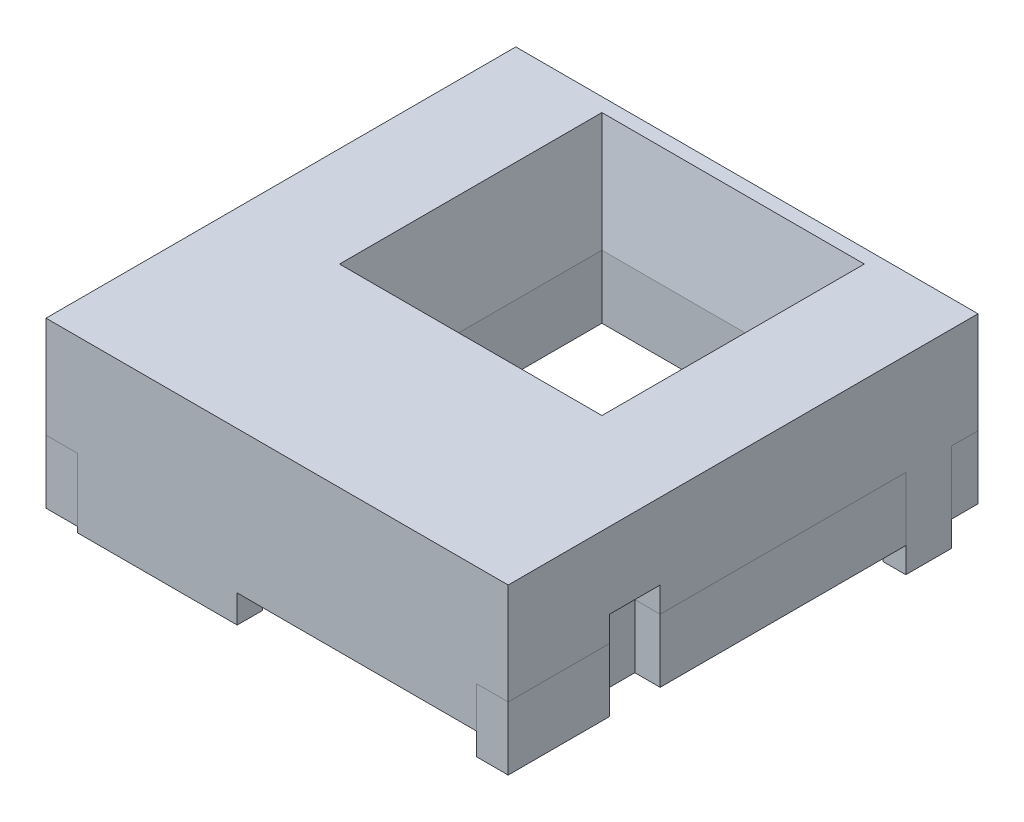
SolidWorks part; units mm, degrees
ref_plane "Front Plane" through (0, 0, 0) normal (0, 0, 1) x (1, 0, 0)
ref_plane "Top Plane" through (0, 0, 0) normal (0, 1, 0) x (1, 0, 0)
ref_plane "Right Plane" through (0, 0, 0) normal (1, 0, 0) x (0, 0, -1)
sketch "Sketch1" plane through (0, 0, 0) normal (0, 1, 0) x (1, 0, 0)
  line L1 (0, 0) -> (36.5, 0)
  line L2 (0, 0) -> (0, -37.1)
  line L3 (0, -37.1) -> (36.5, -37.1)
  line L4 (36.5, 0) -> (36.5, -37.1)
  dimension "D1" = 37.1
  dimension "D2" = 36.5
extrude "Body" add sketch "Sketch1" along normal blind 8
sketch "Sketch2" plane through (0, 0, 0) normal (0, -1, 0) x (-1, 0, 0)
  line L0 (-36.5, 0) -> (0, 0) construction
  line L1 (0, -6.1) -> (-2, -6.1)
  line L2 (0, -6.1) -> (0, -2.1)
  line L3 (0, -2.1) -> (-2, -2.1)
  line L4 (-2, -6.1) -> (-2, -2.1)
  line L5 (-34.5, -29.1) -> (-36.5, -29.1)
  line L6 (-34.5, -29.1) -> (-34.5, -25.1)
  line L7 (-34.5, -25.1) -> (-36.5, -25.1)
  line L8 (-36.5, -29.1) -> (-36.5, -25.1)
  line L10 (0, 0) -> (0, -37.1) construction
  line L11 (0, -37.1) -> (-36.5, -37.1) construction
  line L13 (-36.5, -37.1) -> (-36.5, 0) construction
  point P10 (-1, -2.1)
  dimension "D1" = 2.1
  dimension "D2" = 4
  dimension "D3" = 2
  dimension "D4" = 8
  dimension "D5" = 4
  dimension "D6" = 2
extrude "Female Tabs" cut sketch "Sketch2" against normal blind 2
sketch "Sketch3" plane through (0, 0, 0) normal (0, -1, 0) x (-1, 0, 0)
  line L0 (-36.5, -29.1) -> (-34.5, -29.1) construction
  line L1 (0, -29.1) -> (-1.8, -29.1)
  line L2 (0, -29.1) -> (0, -25.5)
  line L3 (0, -25.5) -> (-1.8, -25.5)
  line L4 (-1.8, -29.1) -> (-1.8, -25.5)
  line L5 (-34.7, -5.7) -> (-36.5, -5.7)
  line L6 (-34.7, -5.7) -> (-34.7, -2.1)
  line L7 (-34.7, -2.1) -> (-36.5, -2.1)
  line L8 (-36.5, -5.7) -> (-36.5, -2.1)
  line L9 (0, -6.1) -> (0, -37.1) construction
  line L10 (-36.5, -25.1) -> (-36.5, 0) construction
  line L11 (0, -2.1) -> (-2, -2.1) construction
  dimension "D1" = 1.8
  dimension "D2" = 3.6
  dimension "D3" = 1.8
  dimension "D4" = 3.6
extrude "Male Tabs" add sketch "Sketch3" along normal blind 7
sketch "Sketch5" plane through (0, 0, 0) normal (0, -1, 0) x (-1, 0, 0)
  line L0 (-36.5, 0) -> (0, 0) construction
  line L1 (-27.2, -2.5) -> (-9.3, -2.5)
  line L2 (-27.2, -2.5) -> (-27.2, -20.4)
  line L3 (-27.2, -20.4) -> (-9.3, -20.4)
  line L4 (-9.3, -2.5) -> (-9.3, -20.4)
  line L5 (-36.5, -2.1) -> (-36.5, 0) construction
  line L6 (0, -6.1) -> (0, -25.5) construction
  line L7 (0, -37.1) -> (-36.5, -37.1) construction
  dimension "D1" = 2.5
  dimension "D2" = 9.3
  dimension "D3" = 9.3
  dimension "D4" = 16.7
extrude "SiPM Window" cut sketch "Sketch5" against normal up to next (8 mm away) draft 10 draft outward yes
sketch "Sketch6" plane through (0, 0, 0) normal (0, -1, 0) x (1, 0, 0)
  line L0 (36.5, 0) -> (0, 0) construction
  line L1 (34, 1.5) -> (29.2, 1.5)
  line L2 (34, 1.5) -> (34, 35.1)
  line L4 (29.2, 1.5) -> (29.2, 22.4)
  line L5 (29.2, 22.4) -> (7.3, 22.4)
  line L9 (7.3, 1.5) -> (2.5, 1.5)
  line L10 (7.3, 1.5) -> (7.3, 22.4)
  line L13 (36.5, 25.1) -> (36.5, 5.7) construction
  line L16 (34, 35.1) -> (2.5, 35.1)
  line L17 (2.5, 35.1) -> (2.5, 1.5)
  line L18 (0, 6.1) -> (0, 25.5) construction
  line L19 (0, 37.1) -> (36.5, 37.1) construction
  line L20 (27.2, 20.4) -> (9.3, 20.4) construction
  line L21 (9.3, 20.4) -> (9.3, 2.5) construction
  line L22 (27.2, 2.5) -> (27.2, 20.4) construction
  dimension "D1" = 1.5
  dimension "D2" = 1.5
  dimension "D3" = 2.5
  dimension "D4" = 2.5
  dimension "D5" = 2
  dimension "D6" = 2
  dimension "D7" = 2
  dimension "D8" = 2
extrude "Cut-Extrude2" cut sketch "Sketch6" against normal offset from surface (6 mm away) 2 up to face at (18.25, 8, 11.45)
sketch "Sketch7" plane through (0, 0, 0) normal (0, -1, 0) x (1, 0, 0)
  line L0 (0, 37.1) -> (36.5, 37.1) construction
  line L1 (34, 35.1) -> (15.1, 35.1)
  line L2 (34, 35.1) -> (34, 37.1)
  line L3 (34, 37.1) -> (15.1, 37.1)
  line L4 (15.1, 35.1) -> (15.1, 37.1)
  line L5 (0, 29.1) -> (0, 37.1) construction
  dimension "D1" = 15.1
extrude "Right Drop" add sketch "Sketch7" along normal blind 3.24
sketch "Sketch8" plane through (0, 0, 0) normal (0, -1, 0) x (1, 0, 0)
  line L1 (15.1, 37.1) -> (2.5, 37.1)
  line L2 (15.1, 37.1) -> (15.1, 35.1)
  line L3 (15.1, 35.1) -> (2.5, 35.1)
  line L4 (2.5, 37.1) -> (2.5, 35.1)
extrude "Left Drop" add sketch "Sketch8" along normal blind 5.44
surface "Surface-Extrude1" parameters "D1"=5
